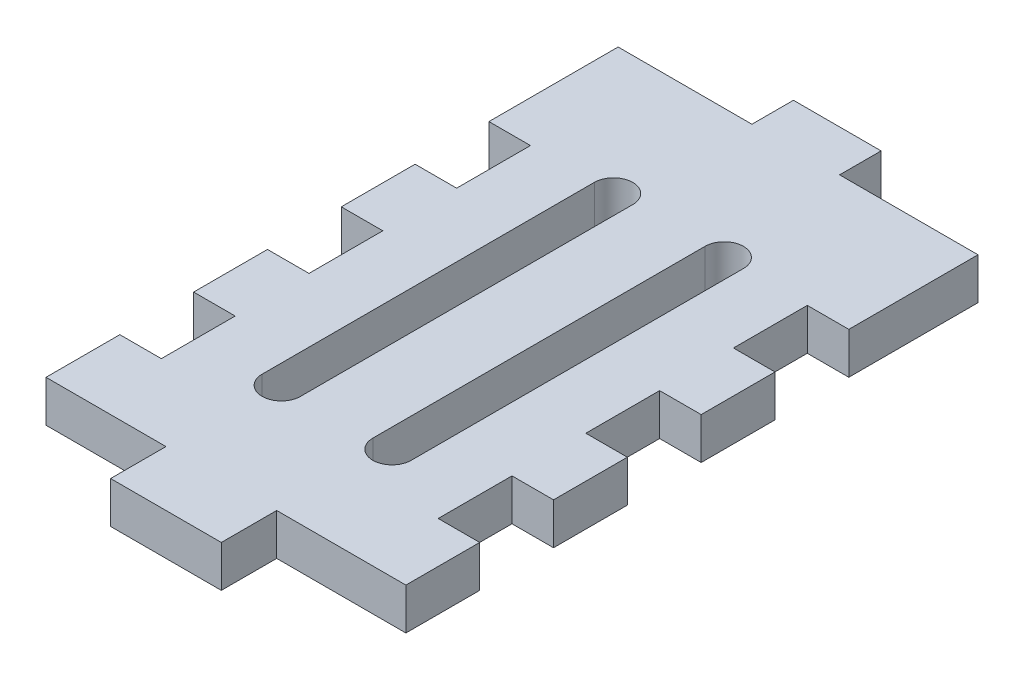
SolidWorks part; units mm, degrees
ref_plane "Front Plane" through (0, 0, 0) normal (0, 0, 1) x (1, 0, 0)
ref_plane "Top Plane" through (0, 0, 0) normal (0, 1, 0) x (1, 0, 0)
ref_plane "Right Plane" through (0, 0, 0) normal (1, 0, 0) x (0, 0, -1)
other "Configuration Table"
sketch "Sketch1" plane through (0, 0, 0) normal (0, 1, 0) x (1, 0, 0)
  line L0 (-7.5833, -18) -> (-7.5833, 18)
  line L11 (0.5, 30) -> (0.5, -30) construction
  line L12 (8.5833, -18) -> (8.5833, 18)
  line L13 (-3.4167, 18) -> (-3.4167, -18)
  line L14 (4.4167, 18) -> (4.4167, -18)
  line L23 (-4.5, 36.5) -> (-4.5, 32)
  line L27 (5, 36.5) -> (5, 32)
  line L28 (-14.5, -30) -> (-6, -30)
  line L30 (-6, -30) -> (-6, -36)
  line L31 (-6, -36) -> (6, -36)
  line L32 (6, -30) -> (6, -36)
  line L33 (6, -30) -> (15.5, -30)
  line L34 (-14.5, -22) -> (-14.5, -14)
  line L35 (-14.5, 32) -> (-19, 32)
  line L37 (-14.5, -30) -> (-19, -30)
  line L39 (-19, 32) -> (-14.5, 32)
  line L40 (-19, 32) -> (-19, 18)
  line L41 (-19, 18) -> (-14.5, 18)
  line L43 (-19, 10) -> (-14.5, 10)
  line L44 (-19, 10) -> (-19, 2)
  line L45 (-19, 2) -> (-14.5, 2)
  line L47 (-19, -6) -> (-14.5, -6)
  line L48 (-19, -6) -> (-19, -14)
  line L49 (-19, -14) -> (-14.5, -14)
  line L51 (-14.5, -30) -> (-19, -30)
  line L53 (-14.5, -22) -> (-19, -22)
  line L54 (-19, -30) -> (-19, -22)
  line L55 (-14.5, -6) -> (-14.5, 2)
  line L56 (-14.5, 10) -> (-14.5, 18)
  line L57 (15.5, -30) -> (20, -30)
  line L58 (20, -30) -> (20, -22)
  line L59 (15.5, -22) -> (20, -22)
  line L60 (15.5, -22) -> (15.5, -14)
  line L61 (20, -14) -> (15.5, -14)
  line L62 (20, -6) -> (20, -14)
  line L63 (20, -6) -> (15.5, -6)
  line L64 (15.5, -6) -> (15.5, 2)
  line L65 (20, 2) -> (15.5, 2)
  line L66 (20, 10) -> (20, 2)
  line L67 (20, 10) -> (15.5, 10)
  line L68 (15.5, 10) -> (15.5, 18)
  line L69 (20, 18) -> (15.5, 18)
  line L70 (20, 32) -> (20, 18)
  line L71 (15.5, 32) -> (20, 32)
  line L72 (-14.5, 32) -> (-4.5, 32)
  line L73 (-4.5, 36.5) -> (5, 36.5)
  line L74 (5, 32) -> (15.5, 32)
  arc A0 (-7.5833, 18) -> (-3.4167, 18) centre (-5.5, 18) cw
  arc A1 (-7.5833, -18) -> (-3.4167, -18) centre (-5.5, -18) ccw
  arc A2 (8.5833, 18) -> (4.4167, 18) centre (6.5, 18) ccw
  arc A3 (8.5833, -18) -> (4.4167, -18) centre (6.5, -18) cw
  point P0 (0, 0)
  point P6 (0, 0)
  point P47 (-16.75, 2)
  dimension "D5" = 66.5
  dimension "D2" = 30
  dimension "D3" = 6
  dimension "D4" = 36
  dimension "D6" = 62
  dimension "D7" = 4.5
  dimension "D8" = 6
  dimension "D9" = 4.5
  dimension "D10" = 8
  dimension "D11" = 10
  dimension "D12" = 8
  dimension "D13" = 8
  dimension "D14" = 8
  dimension "D15" = 8
  dimension "D16" = 8
  dimension "D17" = 14
  dimension "D19" = 12
extrude "Boss-Extrude1" add sketch "Sketch1" along normal blind 4.5 contours L27 L23 L35 L40 L41 L56 L43 L44 L45 L55 L47 L48 L49 L34 L53 L54 L37 L28 L30 L31 L32 L33 L57 L58 L59 L60 L61 L62 L63 L64 L65 L66 L67 L68 L69 L70 L71 A1 L0 A0 L13 L12 A3 L14 region at (0.4765, 0, -0.9742)
